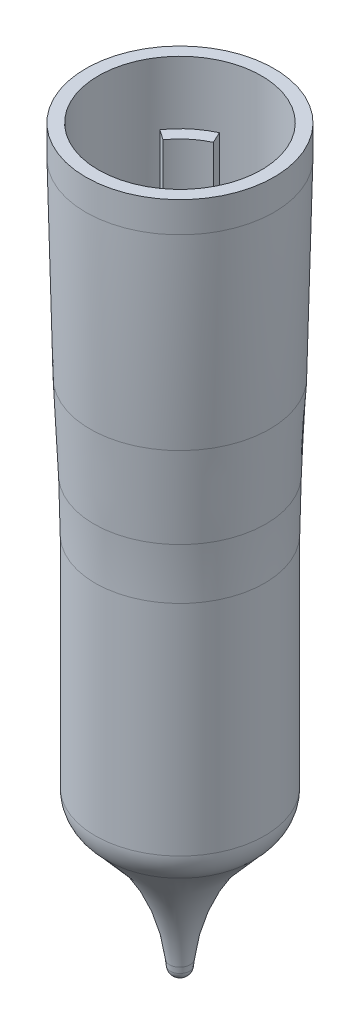
SolidWorks part; units mm, degrees
ref_plane "Front" through (0, 0, 0) normal (0, 0, 1) x (1, 0, 0)
ref_plane "Top" through (0, 0, 0) normal (0, 1, 0) x (1, 0, 0)
ref_plane "Right" through (0, 0, 0) normal (1, 0, 0) x (0, 0, -1)
sketch "Sketch1" plane through (0, 0, 0) normal (0, 1, 0) x (1, 0, 0)
  circle A0 centre (0, 0) radius 4.5
  dimension "D1" = 9
extrude "Boss-Extrude1" add sketch "Sketch1" along normal blind 15
fillet "Fillet1" radius 2 1 edges at (0, 0, 4.5)
sketch "Sketch3" plane through (0, 0, 0) normal (0, 0, 1) x (1, 0, 0)
  line L0 (11.9589, 1.4451) -> (15.9322, 6.5453)
  line L1 (1.5, 13.7613) -> (15.9322, 6.5453)
  line L2 (0, 0.7458) -> (0, 0)
  line L4 (9.0011, 0) -> (0, 0)
  line L5 (4.5, 3.7458) -> (14.7962, 3.7458) construction
  line L6 (1.5, 13.7613) -> (0, 0.7458)
  arc A0 (9.0011, 0) -> (11.9589, 1.4451) centre (9.0011, 3.7493) ccw
  circle A1 centre (9.0011, 3.7493) radius 0.4167
  dimension "D1" = 0.8333
  dimension "D2" = 3.7493
  dimension "D3" = 1.5
  dimension "D4" = 9.0011
  dimension "D5" = 11.9589
  dimension "D6" = 15.9322
  dimension "D7" = 0.7458
  dimension "D8" = 3.7458
  dimension "D9" = 13.7613
extrude "Boss-Extrude2" [suppressed] add sketch "Sketch3" along normal blind 1.5 and the other way blind 1.5
fillet "Fillet4" [suppressed] radius 1
fillet "Fillet2" [suppressed] radius 1
ref_axis "S5 os golenia" through (0, 50.9206, 0) along (0, -1, 0)
fillet "Fillet3" [suppressed] radius 2
pattern_circular "CirPattern1" [suppressed] count 3 over 360 about axis through (0, 50.9206, 0) along (0, -1, 0) of bodies 102
fillet "Fillet5" [suppressed] radius 2
ref_plane "Plane1" through (0, 45, 0) normal (0, 1, 0) x (1, 0, 0)
scale "Scale1" scale about centroid uniform scaling yes scale factor 1.5
sketch "Sketch5" plane through (0, 45, 0) normal (0, 1, 0) x (1, 0, 0)
  circle A0 centre (0, 0) radius 7.5
  dimension "D1" = 15
extrude "Boss-Extrude4" add sketch "Sketch5" against normal blind 10 separate body contours A0
loft "Loft1" add section face at (0, 35, 7.5) section face at (0, 18.6676, 6.75) connector at (-3.7507, 35, 6.4948) connector at (-3.3664, 18.6676, 5.8506)
fillet "Fillet6" radius 330 1 edges at (0, 35, 7.5)
fillet "Fillet7" radius 90 1 edges at (0, 18.6676, 6.75)
sketch "Sketch6" plane through (0, 45, 0) normal (0, 1, 0) x (1, 0, 0)
  circle A2 centre (0, 0) radius 6.5
  circle A3 centre (0, 0) radius 6.5
  dimension "D1" = 1
extrude "Cut-Extrude1" cut sketch "Sketch6" against normal blind 12
ref_point "Point2"
ref_axis "Axis2" through (0, 45, 0) along (1, 0, 0)
sketch "Sketch7" plane through (0, 33, 0) normal (0, 1, 0) x (1, 0, 0)
  line L4 (-5.3245, 3.7282) -> (-4.5053, 3.1547)
  line L5 (-2.3244, 4.9847) -> (-2.747, 5.891)
  circle A0 centre (0, 0) radius 6.5 construction
  arc A4 (-2.747, 5.891) -> (-5.3245, 3.7282) centre (0, 0) ccw
  arc A5 (-2.3244, 4.9847) -> (-4.5053, 3.1547) centre (0, 0) ccw
  dimension "D1" = 6.5
  dimension "D2" = 5.5
  dimension "D3" = 2.3244
  dimension "D4" = 4.5053
extrude "Boss-Extrude5" add sketch "Sketch7" along normal offset from surface (7 mm away) 5 up to face at (0, 45, 6.5)
sketch "Sketch8" plane through (0, -3.8324, 0) normal (0, -1, 0) x (1, 0, 0)
  circle A0 centre (0, 0) radius 1.75
  circle A1 centre (0, 0) radius 3.75 construction
  dimension "D1" = 3.5
extrude "Boss-Extrude6" add sketch "Sketch8" along normal blind 10 draft 6
fillet "Fillet8" radius 0.75 1 edges at (0, -13.8324, -0.699)
fillet "Fillet9" radius 15 1 edges at (0, -3.8324, 1.75)
